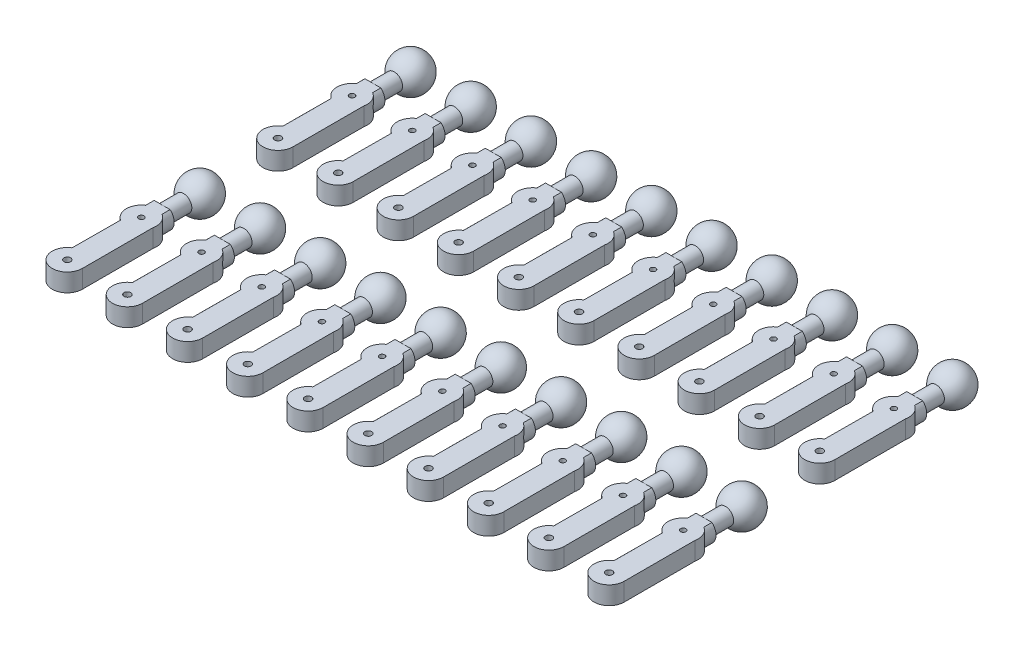
SolidWorks part; units mm, degrees
material "6061 合金"
ref_plane "前视基准面" through (0, 0, 0) normal (0, 0, 1) x (1, 0, 0)
ref_plane "上视基准面" through (0, 0, 0) normal (0, 1, 0) x (1, 0, 0)
ref_plane "右视基准面" through (0, 0, 0) normal (1, 0, 0) x (0, 0, -1)
sketch "草图1" plane through (0, 0, 0) normal (0, 0, 1) x (1, 0, 0)
  line L0 (0, 2.42) -> (0, -2.42)
  circle A0 centre (0, 0) radius 2.42
  dimension "D1" = 4.84
revolve "旋转1" add sketch "草图1" angle 360 about L0 region at (-1.0271, 0, 0)
sketch "草图2" plane through (0, 0, 0) normal (0, 0, 1) x (1, 0, 0)
  circle A0 centre (0, 0) radius 1.1
  dimension "D1" = 2.2
extrude "凸台-拉伸1" add sketch "草图2" along normal blind 17.6064
sketch "草图3" plane through (0, 0, 0) normal (0, 1, 0) x (1, 0, 0)
  line L0 (-1.1, -17.6064) -> (1.1, -17.6064) construction
  circle A0 centre (0, -17.6064) radius 2
  circle A1 centre (0, -17.6064) radius 0.45
  dimension "D1" = 0.9
  dimension "D2" = 4
extrude "切除-拉伸1" cut sketch "草图3" against normal through all both and the other way through all contours A0
extrude "凸台-拉伸2" add sketch "草图3<3>" along normal mid plane 2.4
sketch "草图3<3>" plane through (0, 0, 0) normal (0, 1, 0) x (1, 0, 0) same geometry as "草图3"
ref_axis "基准轴1" through (0, 0, 16.0148) along (0, 0, -1)
ref_plane "基准面1" through (0, 0, 14) normal (0, 0, 1) x (1, 0, 0)
sketch "草图7" plane through (0, 1.2, 0) normal (0, 1, 0) x (1, 0, 0)
  line L1 (0, -17.6064) -> (0.0411, -7.8065) construction
  line L2 (0, -16.0148) -> (0, -2.1556) construction
  line L3 (0, -17.6064) -> (2, -17.6148) construction
  line L4 (2, -17.6148) -> (2.041, -7.8149) construction
  line L5 (2.041, -7.8149) -> (0.0411, -7.8065) construction
  line L6 (0.0411, -7.8065) -> (-1.9589, -7.7981) construction
  line L7 (-1.9589, -7.7981) -> (-2, -17.598) construction
  line L8 (0, -17.6064) -> (-2, -17.598) construction
  circle A0 centre (0, -17.6064) radius 0.45 construction
  circle A1 centre (0, -17.6064) radius 0.45
  circle A2 centre (0.0411, -7.8065) radius 0.36
  circle A3 centre (0.0411, -7.8065) radius 2
  circle A4 centre (0, -17.6064) radius 2 construction
  circle A6 centre (0, -17.6064) radius 2
  circle A8 centre (0, -17.6064) radius 2
  point P19 (0.0205, -12.7064)
  dimension "D1" = 0.72
  dimension "D4" = 4
  dimension "D5" = 0.24
  dimension "D2" = 9.8
  dimension "D3" = 0
extrude "凸台-拉伸8" add sketch "草图7" against normal up to surface (2.4 mm away) contours A3 A2 region at (-1.9024, 1.2, 7.8065) up to face at (0, -1.2, 19.6064)
ref_plane "基准面2" through (0, 0, 5) normal (0, 0, 1) x (1, 0, 0)
sketch "草图9" plane through (0, 0, 5) normal (0, 0, 1) x (1, 0, 0)
  circle A0 centre (0, 0) radius 0.75
  dimension "D1" = 1.5
ref_plane "基准面3" through (0.0205, 1.2, 12.7064) normal (0.0042, 0, -1) x (-1, 0, -0.0042)
sketch "草图10" plane through (0.0205, 1.2, 12.7064) normal (0.0042, 0, -1) x (-1, 0, -0.0042)
  line L0 (0, 0) -> (0, -2.4) construction
  line L2 (-2, -2.4) -> (2, -2.4) construction
  line L3 (-2, -2.4) -> (2, -2.4)
  line L4 (2, 0) -> (-2, 0) construction
  line L5 (2, 0) -> (-2, 0)
  line L6 (-2, 0) -> (-2, -2.4)
  line L7 (2, 0) -> (2, -2.4)
  circle A0 centre (0, -1.2) radius 1.6
  dimension "D1" = 3.2
extrude "凸台-拉伸9" add sketch "草图10" along normal up to surface and the other way up to surface contours L0 L5 A0 L3 | L5 L0 L3 A0 region at (-0.7048, 0, 12.7034) region at (0.7459, 0, 12.7095) up to face at (0.0411, -1.2, 9.8065) other way up to face at (0, -1.2, 19.6064)
ref_axis "基准轴2" through (0.0411, -1.2, 7.8065) along (0, 1, 0)
ref_axis "基准轴3" through (0.0411, -1.2, 7.8065) along (0, 1, 0)
sketch "草图11" plane through (0, 1.2, 0) normal (0, 1, 0) x (1, 0, 0)
  circle A0 centre (0.0411, -7.8065) radius 0.36 construction
  circle A1 centre (0.0411, -7.8065) radius 0.36
extrude "切除-拉伸2" cut sketch "草图11" against normal through all
ref_plane "基准面4" through (0, 0, 10) normal (0, 0, 1) x (1, 0, 0)
sketch "草图12" plane through (0, 0, 10) normal (0, 0, 1) x (1, 0, 0)
  line L0 (0, 0) -> (0, 1.2)
  line L1 (2, 1.2) -> (-2, 1.2) construction
  line L2 (0, 1.2) -> (2, 1.2)
  line L3 (2, 1.2) -> (2, -1.2)
  line L4 (0, 0) -> (0, -1.2)
  line L7 (-2, -1.2) -> (2, -1.2) construction
  line L8 (0, -1.2) -> (2, -1.2)
  dimension "D1" = 2
extrude "凸台-拉伸10" add sketch "草图12" against normal up to body and the other way up to body
ref_plane "基准面5" through (0, 0, 5) normal (0, 0, 1) x (1, 0, 0)
sketch "草图13" plane through (0, 0, 5) normal (0, 0, 1) x (1, 0, 0)
  circle A0 centre (0, 0) radius 1.6
  dimension "D1" = 3.2
extrude "凸台-拉伸11" add sketch "草图13" along normal up to surface (1.5536 mm away) up to face at (-0.2627, 0.0026, 7.2857)
sketch "草图14" plane through (0, 1.2, 0) normal (0, 1, 0) x (1, 0, 0)
  line L1 (-3.6076, -3.9351) -> (3.7968, -3.9351)
  line L2 (-3.6076, -3.9351) -> (-3.6076, -7.9985)
  line L3 (-3.6076, -7.9985) -> (3.7968, -7.9985)
  line L4 (3.7968, -3.9351) -> (3.7968, -7.9985)
extrude "切除-拉伸3" cut sketch "草图14" along normal through all
sketch "草图15" plane through (0, -1.2, 0) normal (0, -1, 0) x (1, 0, 0)
  line L1 (-2.8672, 7.4299) -> (3.0311, 7.4299)
  line L2 (-2.8672, 7.4299) -> (-2.8672, 4.3824)
  line L3 (-2.8672, 4.3824) -> (3.0311, 4.3824)
  line L4 (3.0311, 7.4299) -> (3.0311, 4.3824)
extrude "切除-拉伸4" cut sketch "草图15" along normal through all
pattern_linear "阵列(线性)1" count 10 spacing 8 along (1, 0, 0) count 2 spacing 28 along (0, 0, 1) of bodies 162
equation "\"d\"= 10"
equation "\"l\" = 13.52"
equation "\"L1\"= 8.283"
equation "\"th\"= 52.956771"
equation "\"k\"= 0.8"
equation "\"D1@凸台-拉伸1\"=\"l\"*\"k\""
equation "\"0。42\"=0.84"
equation "\"0。4\"=10"
